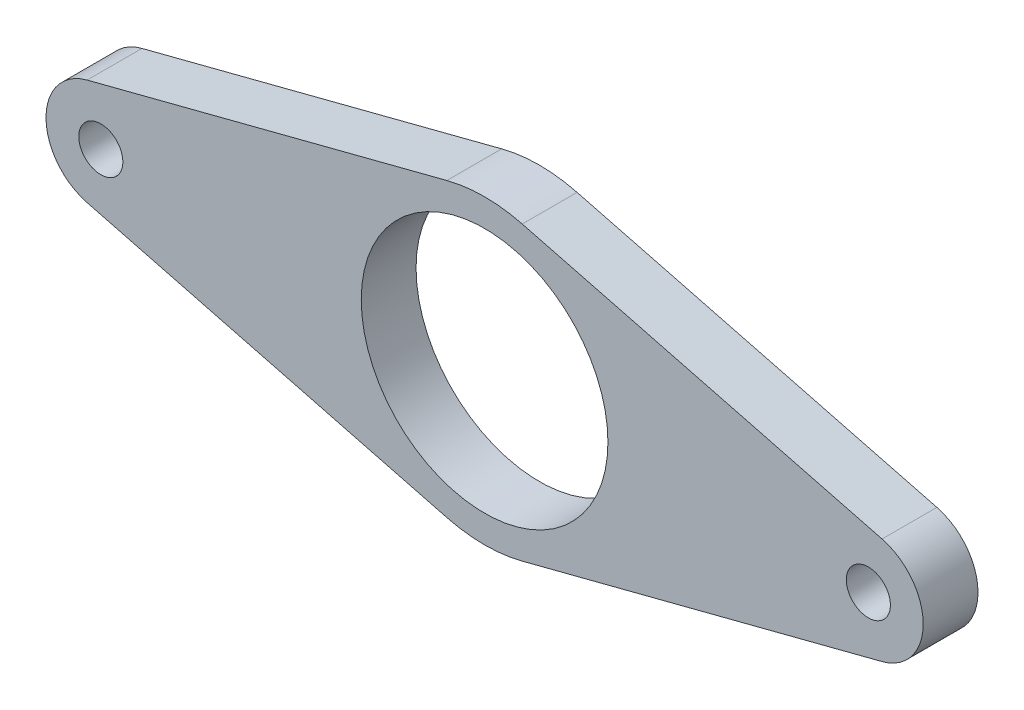
SolidWorks part; units mm, degrees
material "6061-T6 (SS)"
ref_plane "Front Plane" through (0, 0, 0) normal (0, 0, 1) x (1, 0, 0)
ref_plane "Top Plane" through (0, 0, 0) normal (0, 1, 0) x (1, 0, 0)
ref_plane "Right Plane" through (0, 0, 0) normal (1, 0, 0) x (0, 0, -1)
sketch "Sketch1" plane through (0, 0, 0) normal (0, 0, 1) x (1, 0, 0)
  line L0 (-46.0375, 6.1484) -> (-4.3656, 16.908)
  line L1 (-46.0375, -6.1484) -> (-4.3656, -16.908)
  line L2 (46.0375, -6.1484) -> (4.3656, -16.908)
  line L3 (46.0375, 6.1484) -> (4.3656, 16.908)
  arc A0 (-4.3656, -16.908) -> (4.3656, -16.908) centre (0, 0) ccw
  circle A1 centre (-44.45, 0) radius 2.5527
  circle A2 centre (44.45, 0) radius 2.5527
  circle A3 centre (0, 0) radius 14.2875
  arc A4 (-46.0375, 6.1484) -> (-46.0375, -6.1484) centre (-44.45, 0) ccw
  arc A5 (46.0375, 6.1484) -> (46.0375, -6.1484) centre (44.45, 0) cw
  arc A6 (4.3656, 16.908) -> (-4.3656, 16.908) centre (0, 0) ccw
  dimension "D1" = 28.575
  dimension "D2" = 5.1054
  dimension "D3" = 34.925
  dimension ".25" = 6.35
  dimension "D4" = 44.45
  dimension "D5" = 44.45
extrude "Boss-Extrude1" add sketch "Sketch1" along normal blind 6.35 contours L3 A6 L0 A4 L1 A0 L2 A5 A1 A2 A3 region at (-24.933, 10.4879, 0)
